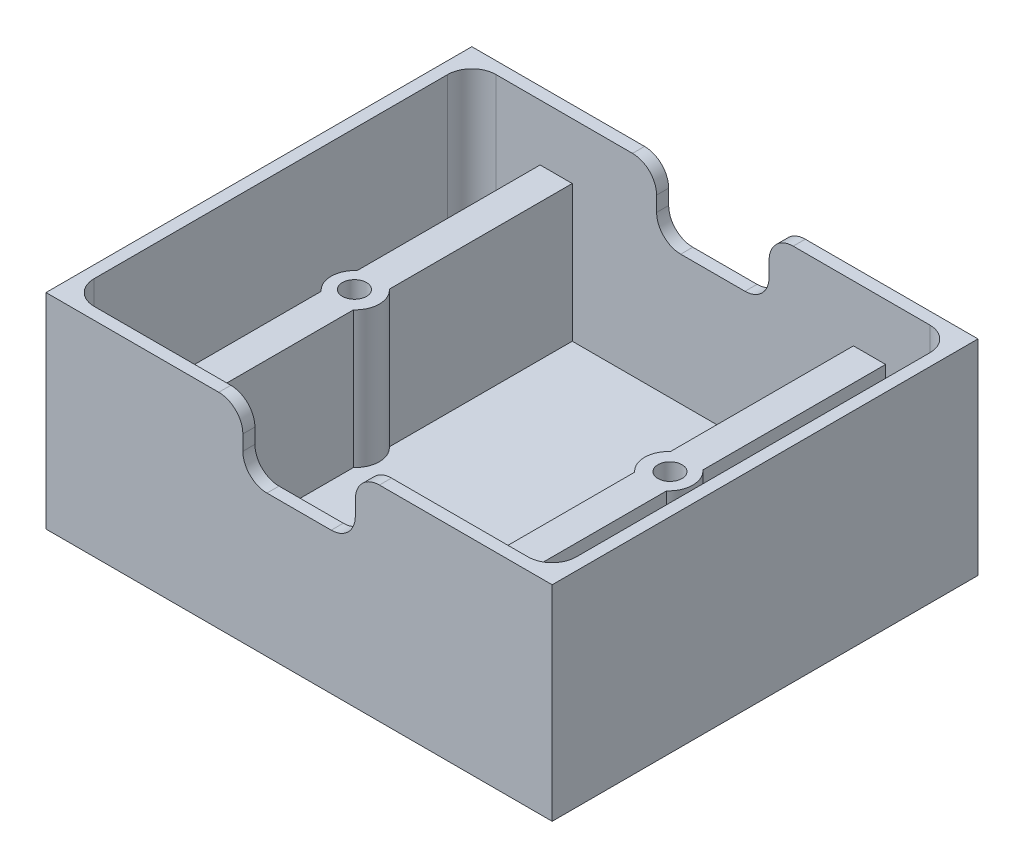
SolidWorks part; units mm, degrees
ref_plane "Front Plane" through (0, 0, 0) normal (0, 0, 1) x (1, 0, 0)
ref_plane "Top Plane" through (0, 0, 0) normal (0, 1, 0) x (1, 0, 0)
ref_plane "Right Plane" through (0, 0, 0) normal (1, 0, 0) x (0, 0, -1)
sketch "Sketch1" plane through (0, 0, 0) normal (0, 1, 0) x (1, 0, 0)
  line L1 (0, 0) -> (60, 0)
  line L2 (0, 0) -> (0, -50)
  line L3 (0, -50) -> (60, -50)
  line L4 (60, 0) -> (60, -50)
  dimension "D1" = 60
  dimension "D2" = 50
extrude "Boss-Extrude1" add sketch "Sketch1" along normal blind 24
shell "Shell1" thickness 1.5 removed face at (30, 24, 25) outward yes
sketch "Sketch2" plane through (0, 0, 0) normal (0, 1, 0) x (1, 0, 0)
  line L0 (60, 0) -> (0, 0) construction
  line L1 (8.5, 0) -> (12.5, 0)
  line L2 (8.5, 0) -> (8.5, -50)
  line L3 (8.5, -50) -> (12.5, -50)
  line L4 (12.5, 0) -> (12.5, -50)
  line L5 (0, -50) -> (60, -50) construction
  line L6 (30, 0) -> (30, -71.172) construction
  line L7 (51.5, -50) -> (47.5, -50)
  line L8 (47.5, 0) -> (47.5, -50)
  line L9 (51.5, 0) -> (47.5, 0)
  line L10 (51.5, 0) -> (51.5, -50)
  dimension "D1" = 4
  dimension "D2" = 17.5
extrude "Boss-Extrude2" add sketch "Sketch2" along normal blind 17
sketch "Sketch3" plane through (0, 0, 0) normal (0, 1, 0) x (1, 0, 0)
  line L0 (-7.5821, -25) -> (66.7821, -25) construction
sketch "Sketch4" plane through (0, 17, 0) normal (0, 1, 0) x (1, 0, 0)
  line L0 (30, -50) -> (30, -57.4435) construction
  line L1 (-7.5821, -25) -> (66.7821, -25) construction
  line L2 (0, -50) -> (60, -50) construction
  circle A0 centre (10.49, -25) radius 3
  circle A2 centre (49.51, -25) radius 3
  dimension "D1" = 6
sketch "Sketch6" plane through (0, 0, 51.5) normal (0, 0, 1) x (1, 0, 0)
  line L0 (30, 24) -> (30, -9.6606) construction
  line L1 (23, 16.1347) -> (37, 16.1347)
  line L2 (23, 16.1347) -> (23, 28.1347)
  line L3 (23, 28.1347) -> (37, 28.1347)
  line L4 (37, 16.1347) -> (37, 28.1347)
  line L5 (-1.5, 24) -> (61.5, 24) construction
  dimension "D1" = 14
  dimension "D2" = 7
  dimension "D3" = 12
extrude "Cut-Extrude2" cut sketch "Sketch6" against normal blind 58
fillet "Fillet1" radius 3 12 edges at (60, 12, 50) (0, 12, 50) (60, 12, 0) (0, 12, 0) (23, 24, -0.75) (23, 16.1347, -0.75) (37, 16.1347, -0.75) (37, 24, -0.75) (23, 24, 50.75) (23, 16.1347, 50.75) (37, 16.1347, 50.75) (37, 24, 50.75)
extrude "Boss-Extrude3" add sketch "Sketch4" against normal up to surface (17 mm away) up to face at (30, 0, 25)
sketch "Sketch7" plane through (0, 17, 0) normal (0, 1, 0) x (1, 0, 0)
  line L0 (30, -50) -> (30, -57.6999) construction
  line L1 (34, -50) -> (26, -50) construction
  circle A0 centre (10.366, -24.9742) radius 1.5
  circle A1 centre (49.634, -24.9742) radius 1.5
  point P6 (10.366, -24.9742)
extrude "Cut-Extrude3" cut sketch "Sketch7" against normal blind 5
